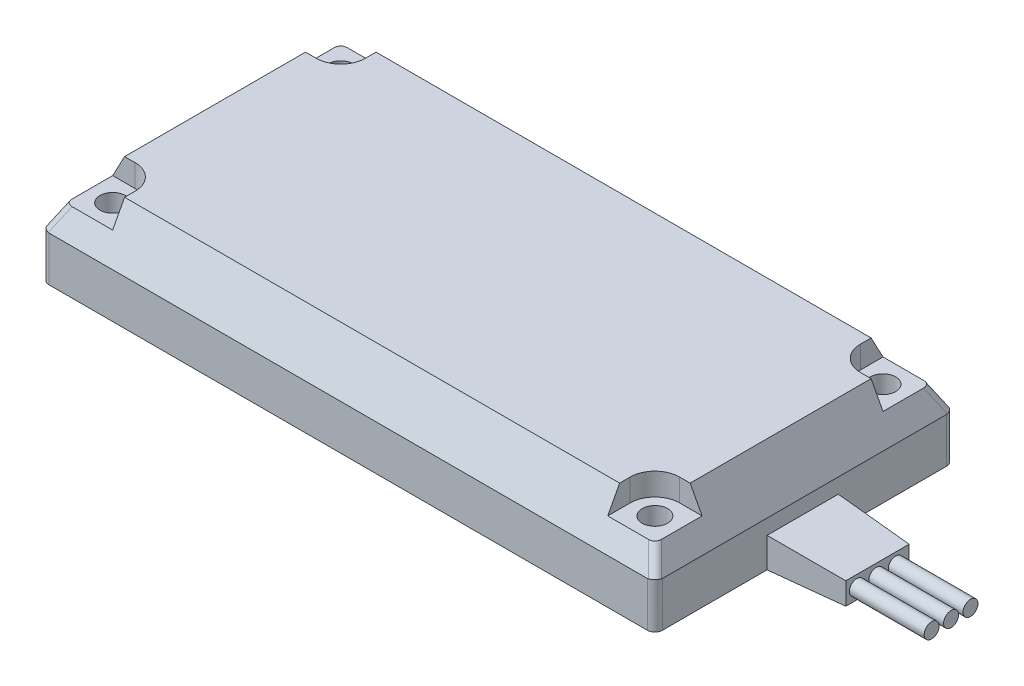
SolidWorks part; units mm, degrees
ref_plane "Front Plane" through (0, 0, 0) normal (0, 0, 1) x (1, 0, 0)
ref_plane "Top Plane" through (0, 0, 0) normal (0, 1, 0) x (1, 0, 0)
ref_plane "Right Plane" through (0, 0, 0) normal (1, 0, 0) x (0, 0, -1)
sketch "Sketch1" plane through (0, 0, 0) normal (0, 1, 0) x (1, 0, 0)
  line L0 (0, 0) -> (41, 0)
  line L1 (41, 0) -> (41, 20)
  line L2 (41, 20) -> (0, 20)
  line L3 (0, 20) -> (0, 0)
extrude "Boss-Extrude1" add sketch "Sketch1" along normal blind 6
chamfer "Chamfer1" distance 3 angle 28 4 edges at (0, 6, -10) (20.5, 6, -20) (41, 6, -10) (20.5, 6, 0) first distance on face at (0, 3, -10) first distance on face at (20.5, 3, -20) first distance on face at (41, 3, -10) first distance on face at (20.5, 3, 0)
sketch "Sketch2" plane through (41, 0, 0) normal (1, 0, 0) x (0, 0, -1)
  line L3 (10, 2) -> (12.2601, 2)
  line L4 (20, 0) -> (20, 3)
  line L5 (20, 3) -> (0, 3)
  line L6 (0, 3) -> (0, 0)
  line L7 (0, 0) -> (20, 0)
  line L9 (10, 2) -> (7.5, 2)
  line L11 (7.5, 0) -> (12.2601, 0)
  line L12 (7.5, 2) -> (7.5, 0)
  line L13 (12.2601, 2) -> (12.2601, 0)
  dimension "D1" = 0
extrude "Boss-Extrude2" add sketch "Sketch2" along normal blind 5 draft 3
sketch "Sketch3" plane through (46, 0, 0) normal (1, 0, 0) x (0, 0, -1)
  circle A0 centre (8.5, 1) radius 0.5
  circle A1 centre (9.8, 1) radius 0.5
  circle A2 centre (11.1, 1) radius 0.5
  dimension "D1" = 3
extrude "Boss-Extrude3" add sketch "Sketch3" along normal blind 5
sketch "Sketch4" plane through (0, 6, 0) normal (0, 1, 0) x (1, 0, 0)
  line L0 (38.6978, 0.6522) -> (37.0478, 0.6522)
  line L1 (37.0478, 0.6522) -> (37.0478, 2.3022)
  line L2 (38.6978, 3.9522) -> (40.3478, 3.9522)
  line L3 (40.3478, 3.9522) -> (40.3478, 2.3022)
  line L4 (37.0478, 17.6978) -> (37.0478, 19.3478)
  line L6 (37.0478, 19.3478) -> (38.6978, 19.3478)
  line L7 (38.6978, 16.0478) -> (40.3478, 16.0478)
  line L8 (40.3478, 16.0478) -> (40.3478, 17.6978)
  line L9 (2.3022, 16.0478) -> (0.6522, 16.0478)
  line L10 (0.6522, 16.0478) -> (0.6522, 17.6978)
  line L11 (3.9522, 17.6978) -> (3.9522, 19.3478)
  line L12 (3.9522, 19.3478) -> (2.3022, 19.3478)
  line L13 (3.9522, 2.3022) -> (3.9522, 0.6522)
  line L14 (3.9522, 0.6522) -> (2.3022, 0.6522)
  line L15 (2.3022, 3.9522) -> (0.6522, 3.9522)
  line L17 (0.6522, 3.9522) -> (0.6522, 2.3022)
  line L18 (38.6978, 0.6522) -> (40.3478, 0.6522)
  line L19 (40.3478, 2.3022) -> (40.3478, 0.6522)
  line L22 (40.3478, 17.6978) -> (40.3478, 19.3478)
  line L23 (38.6978, 19.3478) -> (40.3478, 19.3478)
  line L26 (2.3022, 19.3478) -> (0.6522, 19.3478)
  line L27 (0.6522, 17.6978) -> (0.6522, 19.3478)
  line L28 (0.6522, 2.3022) -> (0.6522, 0.6522)
  line L29 (2.3022, 0.6522) -> (0.6522, 0.6522)
  arc A0 (37.0478, 17.6978) -> (38.6978, 16.0478) centre (38.6978, 17.6978) ccw
  arc A1 (3.9522, 17.6978) -> (2.3022, 16.0478) centre (2.3022, 17.6978) cw
  arc A2 (37.0478, 2.3022) -> (38.6978, 3.9522) centre (38.6978, 2.3022) cw
  arc A3 (3.9522, 2.3022) -> (2.3022, 3.9522) centre (2.3022, 2.3022) ccw
extrude "Cut-Extrude3" cut sketch "Sketch4" against normal blind 1.5
sketch "Sketch5" plane through (0, 4.5, 0) normal (0, 1, 0) x (1, 0, 0)
  circle A0 centre (38.6251, 2.3749) radius 0.85
  circle A1 centre (38.6251, 17.6251) radius 0.85
  circle A2 centre (2.3749, 17.6251) radius 0.85
  circle A3 centre (2.3749, 2.3749) radius 0.85
extrude "Cut-Extrude4" cut sketch "Sketch5" against normal through all
fillet "Fillet1" radius 0.5 8 edges at (0.3988, 3.75, -19.6012) (0, 1.5, -20) (0.3988, 3.75, -0.3988) (0, 1.5, 0) (40.6012, 3.75, -0.3988) (40.6012, 3.75, -19.6012) (41, 1.5, -20) (41, 1.5, 0)
